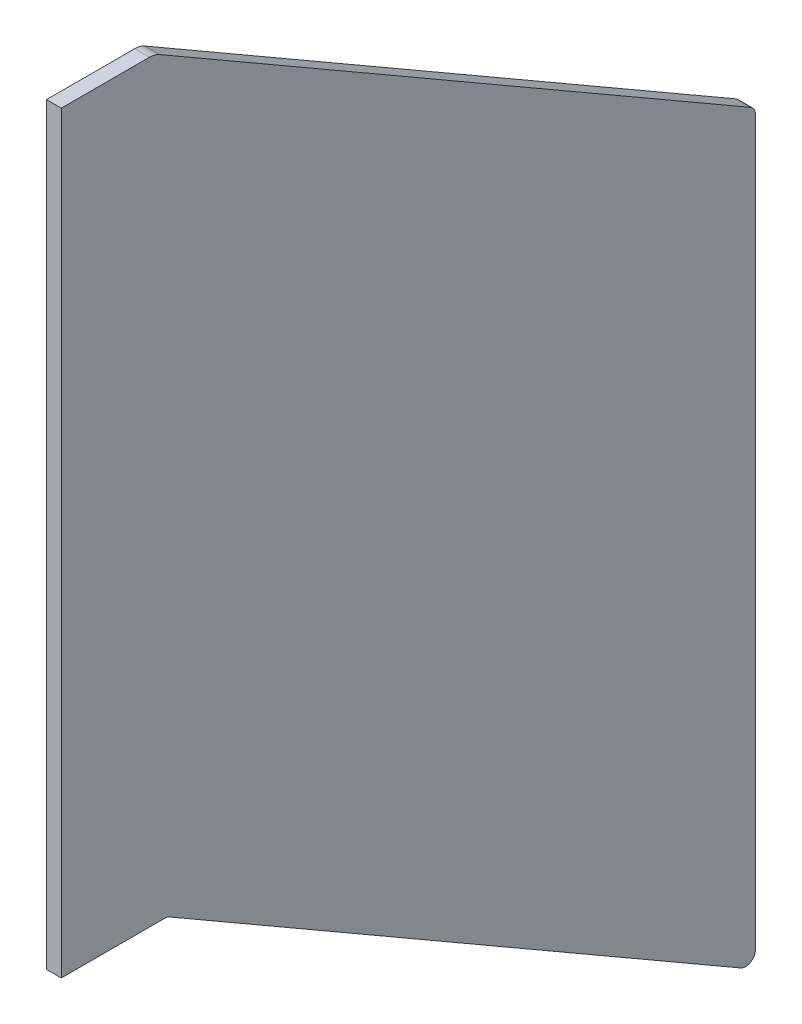
SolidWorks part; units mm, degrees
material "AISI 304"
ref_plane "Спереди" through (0, 0, 0) normal (0, 0, 1) x (1, 0, 0)
ref_plane "Сверху" through (0, 0, 0) normal (0, 1, 0) x (1, 0, 0)
ref_plane "Справа" through (0, 0, 0) normal (1, 0, 0) x (0, 0, -1)
sketch "Эскиз1" plane through (0, 0, 0) normal (1, 0, 0) x (0, 0, -1)
  line L0 (0, 0) -> (10.5, 0)
  line L1 (11, -0.134) -> (69, -33.6203)
  line L2 (70.5, -32.7543) -> (70.5, 40.7043)
  line L3 (70, 41.5703) -> (9.9641, 76.2321)
  line L4 (8.9641, 76.5) -> (0, 76.5)
  line L5 (0, 76.5) -> (0, 0)
  arc A0 (69, -33.6203) -> (70.5, -32.7543) centre (69.5, -32.7543) ccw
  arc A1 (70.5, 40.7043) -> (70, 41.5703) centre (69.5, 40.7043) ccw
  arc A2 (11, -0.134) -> (10.5, 0) centre (10.5, -1) ccw
  arc A3 (9.9641, 76.2321) -> (8.9641, 76.5) centre (8.9641, 74.5) ccw
  point P17 (9.5, 76.5)
  dimension "D5" = 1
  dimension "D6" = 1
  dimension "D7" = 2
  dimension "D1" = 9.5
  dimension "D2" = 76.5
  dimension "D3" = 30
  dimension "D4" = 70.5
  dimension "D8" = 10.5
base flange "Базовая кромка1" sketch "Эскиз1" thickness 1.5 reverse thickness direction no parameters "D1"=1
sketch "Сгиб-Линии1" [suppressed] plane through (0, 0, 0) normal (0, 1, 0) x (1, 0, 0)
sketch "Граничная рамка1" [suppressed] plane through (0, 0, 0) normal (0, 1, 0) x (1, 0, 0)
sheet metal parameters "Листовой металл1" thickness 1.5 parameters "D1"=1
flat pattern "Развертка1" [suppressed]
sketch "Сгиб-Линии2" plane through (0, 0, 0) normal (0, 1, 0) x (1, 0, 0)
sketch3d "Граничная рамка2" [suppressed]
  line L0 (59.9999, -32.754, 0) -> (60, 77.4999, 0) construction
  line L1 (-10.5, -32.7539, 0) -> (-10.4999, 77.5, 0) construction
  line L2 (59.9999, -32.754, 0) -> (-10.5, -32.7539, 0) construction
  line L3 (60, 77.4999, 0) -> (-10.4999, 77.5, 0) construction
